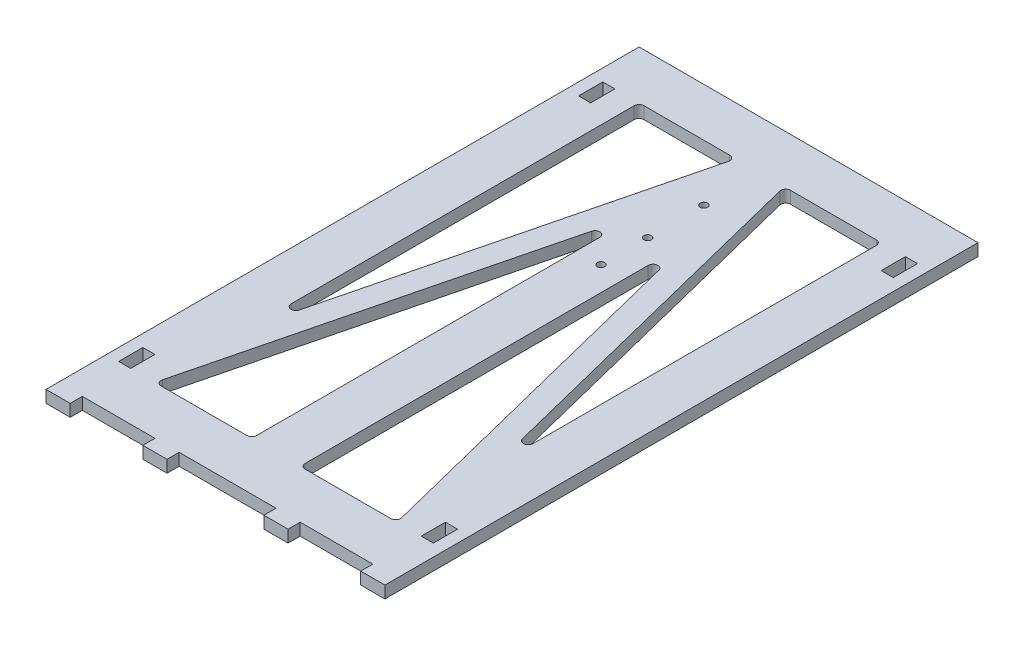
SolidWorks part; units mm, degrees
material "Beech"
ref_plane "Front Plane" through (0, 0, 0) normal (0, 0, 1) x (1, 0, 0)
ref_plane "Top Plane" through (0, 0, 0) normal (0, 1, 0) x (1, 0, 0)
ref_plane "Right Plane" through (0, 0, 0) normal (1, 0, 0) x (0, 0, -1)
sketch "Sketch1" plane through (0, 0, 0) normal (0, 1, 0) x (1, 0, 0)
  line L0 (0, 0) -> (177.8, 0)
  line L1 (0, 0) -> (0, 304.8)
  line L2 (177.8, 0) -> (177.8, 304.8)
  line L3 (0, 304.8) -> (177.8, 304.8)
  line L4 (0, 0) -> (12.7, 0)
  line L5 (0, 0) -> (0, -6.35)
  line L6 (12.7, 0) -> (12.7, -6.35)
  line L7 (0, -6.35) -> (12.7, -6.35)
  line L8 (50.8, 0) -> (63.5, 0)
  line L9 (50.8, 0) -> (50.8, -6.35)
  line L10 (63.5, 0) -> (63.5, -6.35)
  line L11 (50.8, -6.35) -> (63.5, -6.35)
  line L12 (114.3, 0) -> (127, 0)
  line L13 (114.3, 0) -> (114.3, -6.35)
  line L14 (127, 0) -> (127, -6.35)
  line L15 (114.3, -6.35) -> (127, -6.35)
  line L16 (177.8, 0) -> (165.1, 0)
  line L17 (177.8, 0) -> (177.8, -6.35)
  line L18 (165.1, 0) -> (165.1, -6.35)
  line L19 (177.8, -6.35) -> (165.1, -6.35)
  line L20 (165.1, 279.4) -> (171.45, 279.4)
  line L21 (165.1, 279.4) -> (165.1, 266.7)
  line L22 (171.45, 279.4) -> (171.45, 266.7)
  line L23 (165.1, 266.7) -> (171.45, 266.7)
  line L24 (6.35, 279.4) -> (12.7, 279.4)
  line L25 (6.35, 279.4) -> (6.35, 266.7)
  line L26 (12.7, 279.4) -> (12.7, 266.7)
  line L27 (6.35, 266.7) -> (12.7, 266.7)
  line L28 (6.35, 38.1) -> (12.7, 38.1)
  line L29 (6.35, 38.1) -> (6.35, 25.4)
  line L30 (12.7, 38.1) -> (12.7, 25.4)
  line L31 (6.35, 25.4) -> (12.7, 25.4)
  line L32 (171.45, 38.1) -> (165.1, 38.1)
  line L33 (171.45, 38.1) -> (171.45, 25.4)
  line L34 (165.1, 38.1) -> (165.1, 25.4)
  line L35 (171.45, 25.4) -> (165.1, 25.4)
  line L36 (76.2, 279.4) -> (25.4, 279.4)
  line L37 (25.4, 279.4) -> (25.4, 76.2)
  line L38 (25.4, 76.2) -> (76.2, 279.4)
  line L39 (101.6, 279.4) -> (152.4, 279.4)
  line L40 (152.4, 279.4) -> (152.4, 76.2)
  line L41 (152.4, 76.2) -> (101.6, 279.4)
  line L42 (76.2, 228.6) -> (76.2, 25.4)
  line L43 (76.2, 25.4) -> (25.4, 25.4)
  line L44 (25.4, 25.4) -> (76.2, 228.6)
  line L45 (101.6, 228.6) -> (101.6, 25.4)
  line L46 (101.6, 25.4) -> (152.4, 25.4)
  line L47 (152.4, 25.4) -> (101.6, 228.6)
  circle A1 centre (88.9, 249.9) radius 1.935
  circle A2 centre (88.9, 220.4) radius 1.935
  circle A3 centre (88.9, 195.9) radius 1.935
  point P21 (88.9, 304.8)
  dimension "D8" = 12.7
  dimension "D6" = 3.87
  dimension "D1" = 177.8
  dimension "D2" = 304.8
  dimension "D3" = 29.5
  dimension "D4" = 54.9
  dimension "D5" = 24.5
  dimension "D7" = 6.35
  dimension "D9" = 25.4
  dimension "D10" = 50.8
  dimension "D11" = 50.8
  dimension "D12" = 12.7
  dimension "D13" = 25.4
  dimension "D14" = 6.35
  dimension "D15" = 6.35
  dimension "D16" = 12.7
  dimension "D17" = 203.2
  dimension "D18" = 50.8
  dimension "D19" = 50.8
  dimension "D20" = 12.7
extrude "Front Panel" add sketch "Sketch1" along normal blind 6.35 contours L3 L1 L0 L2 L33 L35 L34 L32 L31 L29 L28 L30 L19 L15 L27 L25 L24 L26 L23 L21 L20 L22 | L0 | L0 | L7 L0 | L0 region at (88.9, 0, -152.3259) region at (6.35, 0, 3.175) region at (57.15, 0, 3.175) region at (171.45, 0, 3.175) region at (120.65, 0, 3.175)
fillet "Fillet1" radius 2.54 12 edges at (25.4, 3.175, -279.4) (76.2, 3.175, -279.4) (25.4, 3.175, -76.2) (25.4, 3.175, -25.4) (76.2, 3.175, -25.4) (76.2, 3.175, -228.6) (101.6, 3.175, -228.6) (101.6, 3.175, -25.4) (152.4, 3.175, -25.4) (152.4, 3.175, -76.2) (152.4, 3.175, -279.4) (101.6, 3.175, -279.4)
equation "\"CageLeftBottomEdge\"=22.11mm"
equation "\"CageLeftTopEdge\"=22.11mm"
equation "\"CageRightBottomEdge\"=21.63mm"
equation "\"CageRightTopEdge\"=21.63mm"
equation "\"CageHeight\"=86.04mm"
equation "\"CageLength\"=73.76mm"
equation "\"CageTopScrewClearance\"=10mm"
equation "\"CageBottomScrewClearance\"=25mm"
equation "\"CageLeftTopDepth\"= 11.65mm"
equation "\"CageLeftBottomDepth\"=11.11mm"
equation "\"CageLeftTopHeight\"=8.56175mm"
equation "\"CageLeftBottomHeight\"=16mm"
equation "\"CageRightTopDepth\"= 11.05mm"
equation "\"CageRightBottomDepth\"=10.58mm"
equation "\"CageRightTopHeight\"=9.6mm"
equation "\"CageRightBottomHeight\"=15.49mm"
equation "\"CageLeftTopChannelDepth\"=2.41908mm"
equation "\"CageLeftBottomChannelDepth\"=2.588mm"
equation "\"CageLeftChannelHeight\"=11.7mm"
equation "\"CageRightTopChannelDepth\"=2.32mm"
equation "\"CageRightBottomChannelDepth\"=2.318mm"
equation "\"CageRightChannelHeight\"=10mm"
equation "\"CageChanRelHeight\"=23.99mm"
equation "\"CageChanRelDepth\"=5.492mm"
equation "\"CageChamberRadius\"=16.261mm"
equation "\"CageScrewDiameter\"=4.8mm"
equation "\"CageSetScrewDiameter\"=3.5mm"
equation "\"CageAxleRadius\"=6.639mm"
equation "\"CageAxleKeyHeight\"=1.619mm"
equation "\"CageAxleKeyWidth\"=2.662mm"
equation "\"CageHoseWindowWidth\"=16.29mm"
equation "\"CageHoseWindowHeight\"=26.5mm"
equation "\"CageHoseWindow-Edge\"=8.89mm"
equation "\"CageScrew-VerticalEdge\"=5.0mm"
equation "\"CageScrew-HorizontalEdge\"=7.5mm"
equation "\"CageScrew-HoseCornerScrewEdge\"=4.45mm"
equation "\"CageAxle-BottomEdge\"=56.05mm"
equation "\"CageAxle-FrontEdge\"=46.03mm"
equation "\"CageBackSetScrew-Axle\"=40mm"
equation "\"CageFrontSetScrew-Axle\"=22mm"
equation "\"CageVelocityWindow-BackEdge\"=34.8mm"
equation "\"CageVelocityWindow-BottomEdge\"=27.55mm"
equation "\"CageVelocityWindowHeight\"=22.29mm"
equation "\"CageVelocityWindowWidth\"=12.61mm"
equation "\"TriggerSlot-BottomEdge\"=6.35mm"
equation "\"TriggerSlot-FrontEdge\"=15mm"
equation "\"TriggerSlotSize\"=6.7mm"
equation "\"TriggerRackOffset\"=.236224in"
equation "\"TriggerSlotSizeInt\"=.25in"
equation "\"MotorMountLegLength\"=.25in"
equation "\"GearOffset\"=.264907in"
equation "\"TriggerSlotSpacing\"=.25in"
equation "\"TriggerMiniSlotWidth\"=3.5mm"
equation "\"TriggerRackWidth\"=6.5mm"
equation "\"whitemotordepth\"=11.27mm"
equation "\"whitemotorbackdepth\"=3.845mm"
equation "\"whitemotoraxledepth\" = 3.5mm"
equation "\"whitemotoraxleoffset\"=11.4mm"
equation "\"whitemotorwidth\"=12.07mm"
equation "\"whitemotorheight\"=16.68mm"
equation "\"whitemotorcylinderlength\" =13.04mm"
equation "\"whitemotorcylinderradius\"=3.845mm"
equation "\"whitemotorcylinderoffset\"=2.35mm"
equation "\"whitemotorcutoutlength\"=1.88mm"
equation "\"whitemotorouterrad\"=5mm"
equation "\"whitemotorinnerrad\"=2.95mm"
equation "\"elasticracklength\"=2in"
equation "\"elasticrackpegsize\"=.25in"
equation "\"elasticrackpegbuffer\"=.125in"
equation "\"elasticrackpegspacing\"=1.76476378in"
equation "\"elasticbaybuffer\"=.25in"
equation "\"elasticdepth\"=.125in"
equation "\"elasticbaydepth\"=.75in"
equation "\"motormountwidth\"=12mm"
equation "\"motormountcornerfillet\"=3mm"
equation "\"pandiscradius\"=14in"
equation "\"towermaterialwidth\"=.25in"
equation "\"towerslotlength\"=.5in"
equation "\"towermarkerspace\"=5in"
equation "\"towerslothorizoffset\"=1in"
equation "\"towerslothorizspacing\"=2in"
equation "\"towerslotvertoffset\"=3in"
equation "\"towerslotvertspacing\"=1in"
equation "\"towerheight\"=12in"
equation "\"towerupslot\"=1in"
equation "\"D1@Sketch1\"=(\"towerslothorizoffset\"+\"towerslothorizspacing\"+\"towerslotlength\")*2"
equation "\"D2@Sketch1\"=\"towerheight\""
equation "\"D3@Sketch1\"=\"ajax4020gap\""
equation "\"D4@Sketch1\"=\"ajax4020gap\"+1in"
equation "\"D5@Sketch1\"=\"ajax4010gap\""
equation "\"D6@Sketch1\"=\"ajaxaxlesize\""
equation "\"D7@Sketch1\"=\"towermaterialwidth\""
equation "\"toweraxle\"=.5in"
equation "\"D8@Sketch1\"=\"towerslotlength\""
equation "\"D9@Sketch1\"=\"towerupslot\""
equation "\"D10@Sketch1\"=\"towerslothorizspacing\""
equation "\"D11@Sketch1\"=\"towerslothorizspacing\""
equation "\"D12@Sketch1\"=\"towerslotlength\""
equation "\"D13@Sketch1\"=\"towerupslot\""
equation "\"D1@Front Panel\"=\"towermaterialwidth\""
equation "\"stepperouterrad\"=10mm"
equation "\"stepperscrewsize\"=3.45mm"
equation "\"stepperscrewc2c\"=49.5mm"
equation "\"stepperdepthoffset\"=24mm"
equation "\"stepperhorizoffset\"=22.91mm"
equation "\"shaftslotOD\"=18.8mm"
equation "\"shaftslotID\"=13.28mm"
equation "\"shaftkeywidth\"=2.67mm"
equation "\"shaftkeydepth\"=1.8mm"
equation "\"shaftcollartotaldepth\"=12.5mm"
equation "\"shaftsquaredepth\"=6mm"
equation "\"shaftsetscrewsize\"=3.5mm"
equation "\"shaftkeytightdepth\"=1.85mm"
equation "\"shaftslottightID\"=12.78mm"
equation "\"shaftsetscrewoffset\"=9mm"
equation "\"cagecollartotaldepth\"=10mm"
equation "\"cagecollartotalwidth\"=35mm"
equation "\"cagecollarbasedepth\"=4mm"
equation "\"ajaxaxlesize\"=3.87mm"
equation "\"ajax4020gap\"=29.5mm"
equation "\"ajax4010gap\"=24.5mm"
equation "\"D14@Sketch1\"=\"towermaterialwidth\""
equation "\"D15@Sketch1\"=\"towermaterialwidth\""
equation "\"D16@Sketch1\"=\"toweraxle\""
equation "\"towerspeedwidth\"=2in"
equation "\"towerspeedheight\"=8in"
equation "\"towerspeedgap\"=2in"
equation "\"stepperaxleflat\"=.037in"
equation "\"stepperaxlerad\"=0.11811024in"
equation "\"ajaxinnercut\"=2.3mm"
equation "\"ajaxwidth\"=6.1mm"
equation "\"ajaxdiametral\"=25.8854"
equation "\"ajaxcutoutdepth\"=2.3mm"
equation "\"ajax20hubbuffer\"=6.1mm"
equation "\"ajax20hubholeoffset\"=.19685in"
equation "\"ajax20hubholesize\"=.059055in"
equation "\"ajax20cutoutint\"=13.4mm"
equation "\"ajax40hubholesize\"=7.21mm"
equation "\"ajax40hubholeoffset\"=10mm"
equation "\"ajax40hubbuffer\"=8.9mm"
equation "\"ajax40cutoutint\"=32.6mm"
equation "\"bearingpandiscrad\"=6.8in"
equation "\"bearingpandiscang\"=48.75deg"
equation "\"bearingclearholedist\"=4.7345in"
equation "\"bearingclearholesize\"=.5in"
equation "\"bearingclearholeang\"=22.5deg"
equation "\"bearingmountholedist\"=4.25in"
equation "\"bearingwirehole\"=1.5in"
equation "\"no6diam\"=.146in"
equation "\"D17@Sketch1\"=\"towerspeedheight\""
equation "\"D19@Sketch1\"=\"towerspeedgap\""
equation "\"D18@Sketch1\"=\"towerspeedwidth\""
equation "\"D20@Sketch1\"=\"toweraxle\""
equation "\"gearhubintdiam\"=30mm"
equation "\"gearhubintwid\"=15mm"
equation "\"shortconangle\"=20deg"
equation "\"shortconlen\"=.875in"
equation "\"longconlen\"=1.25in"
equation "\"longconangle\"=15deg"
